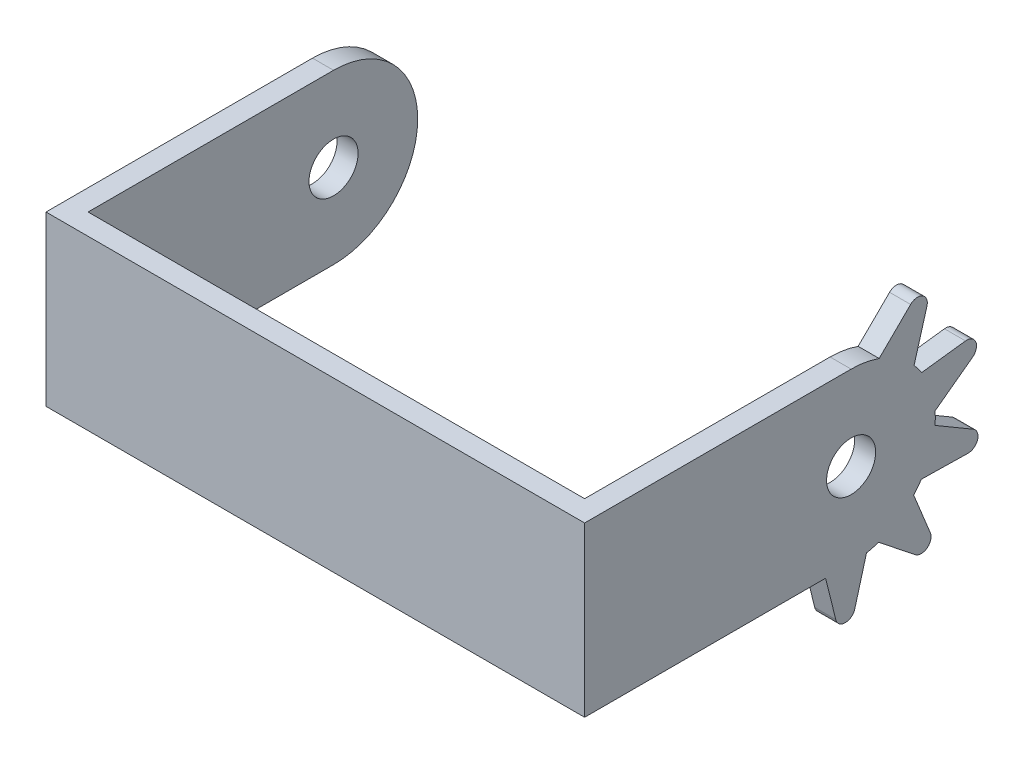
SolidWorks part; units mm, degrees
material "ABS"
ref_plane "前视基准面" through (0, 0, 0) normal (0, 0, 1) x (1, 0, 0)
ref_plane "上视基准面" through (0, 0, 0) normal (0, 1, 0) x (1, 0, 0)
ref_plane "右视基准面" through (0, 0, 0) normal (1, 0, 0) x (0, 0, -1)
sketch "草图2" plane through (0, 0, 0) normal (0, 1, 0) x (1, 0, 0)
  line L0 (0, 0) -> (38.4, 0)
  line L1 (38.4, 0) -> (38.4, 25)
  line L2 (38.4, 25) -> (36.9, 25)
  line L3 (36.9, 25) -> (36.9, 1.5)
  line L4 (36.9, 1.5) -> (1.5, 1.5)
  line L5 (1.5, 1.5) -> (1.5, 25)
  line L6 (1.5, 25) -> (0, 25)
  line L7 (0, 25) -> (0, 0)
  dimension "D1" = 1.5
  dimension "D2" = 25
  dimension "D3" = 1.5
  dimension "D4" = 38.4
extrude "凸台-拉伸2" add sketch "草图2" along normal blind 12
fillet "圆角1" radius 6 4 edges at (0.75, 0, -25) (0.75, 12, -25) (37.65, 0, -25) (37.65, 12, -25)
sketch "草图5" plane through (0, 0, 0) normal (-1, 0, 0) x (0, 0, 1)
  circle A0 centre (-19, 6) radius 1.75
  dimension "D1" = 3.5
extrude "切除-拉伸3" cut sketch "草图5" against normal up to next
sketch "草图6" plane through (38.4, 0, 0) normal (1, 0, 0) x (0, 0, -1)
  circle A0 centre (19, 6) radius 1.75
  dimension "D1" = 3.5
extrude "切除-拉伸4" cut sketch "草图6" against normal up to surface (1.5 mm away) up to face at (36.9, 6, -13.6971)
sketch "草图7" plane through (38.4, 0, 0) normal (1, 0, 0) x (0, 0, -1)
  line L0 (20.9997, 11.657) -> (23.2414, 13.8706)
  line L1 (24.4061, 13.1794) -> (23.4884, 9.9817)
  line L2 (19, 6) -> (19, 11.1726) construction
  line L3 (23.7333, 13.3725) -> (22.3504, 10.9774) construction
  line L4 (27.6595, 8.4048) -> (24.9848, 6.4266)
  line L5 (24.0302, 9.2706) -> (27.1563, 9.6622)
  line L6 (27.334, 2.6363) -> (24.0077, 2.6951)
  line L7 (24.9818, 5.5326) -> (27.7002, 3.9402)
  line L8 (23.5641, -1.7421) -> (20.961, 0.3295)
  line L9 (23.4611, 1.9877) -> (24.6484, -0.9305)
  line L10 (17.9079, -2.9206) -> (17.1038, 0.3075)
  line L11 (20.0967, 0.1011) -> (19.2621, -2.9369)
  arc A0 (25, 6) -> (19, 12) centre (19, 6) ccw construction
  arc A1 (20.9997, 11.657) -> (23.4884, 9.9817) centre (19, 6) cw
  arc A2 (24.4061, 13.1794) -> (23.2414, 13.8706) centre (23.7333, 13.3725) ccw
  arc A3 (24.0302, 9.2706) -> (24.9848, 6.4266) centre (19, 6) cw
  arc A4 (27.6595, 8.4048) -> (27.1563, 9.6622) centre (27.2433, 8.9676) ccw
  arc A5 (24.9818, 5.5326) -> (24.0077, 2.6951) centre (19, 6) cw
  arc A6 (27.334, 2.6363) -> (27.7002, 3.9402) centre (27.3464, 3.3361) ccw
  arc A7 (23.4611, 1.9877) -> (20.961, 0.3295) centre (19, 6) cw
  arc A8 (23.5641, -1.7421) -> (24.6484, -0.9305) centre (24, -1.1943) ccw
  arc A9 (20.0967, 0.1011) -> (17.1038, 0.3075) centre (19, 6) cw
  arc A10 (17.9079, -2.9206) -> (19.2621, -2.9369) centre (18.5871, -2.7515) ccw
  point P12 (25.1435, 15.7489)
  point P35 (19, 6)
  dimension "D3" = 0.7
  dimension "D1" = 3
  dimension "D2" = 6
  dimension "D5" = 30
  dimension "D6" = 5
extrude "凸台-拉伸3" add sketch "草图7" against normal up to surface (1.5 mm away) up to face at (36.9, 6, -20.75)
